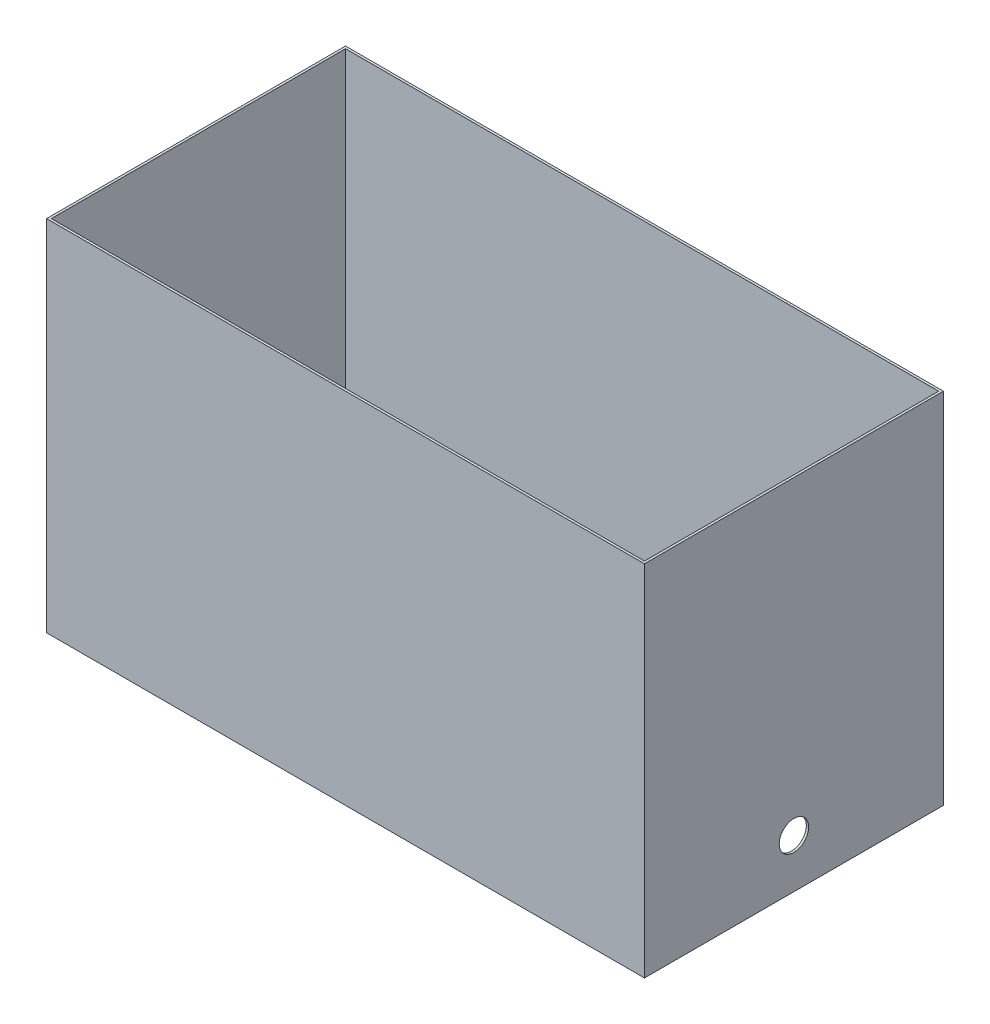
SolidWorks part; units mm, degrees
material "Galvanized Steel"
ref_plane "Front Plane" through (0, 0, 0) normal (0, 0, 1) x (1, 0, 0)
ref_plane "Top Plane" through (0, 0, 0) normal (0, 1, 0) x (1, 0, 0)
ref_plane "Right Plane" through (0, 0, 0) normal (1, 0, 0) x (0, 0, -1)
sketch "Sketch1" plane through (0, 0, 0) normal (0, 1, 0) x (1, 0, 0)
  line L0 (-252, 125) -> (252, 125)
  line L1 (-254, -127) -> (254, -127)
  line L2 (-254, -127) -> (-254, 127)
  line L3 (-254, 127) -> (254, 127)
  line L4 (254, -127) -> (254, 127)
  line L5 (-254, -127) -> (254, 127) construction
  line L6 (-254, 127) -> (254, -127) construction
  line L7 (252, -125) -> (252, 125)
  line L8 (-252, -125) -> (252, -125)
  line L9 (-252, -125) -> (-252, 125)
  point P0 (0, 0)
  dimension "D1" = 254
  dimension "D2" = 508
  dimension "D3" = 2
extrude "Boss-Extrude1" add sketch "Sketch1" along normal blind 304.8
sketch "Sketch2" plane through (-254, 0, 0) normal (-1, 0, 0) x (0, 0, 1)
  line L0 (0, 41.4) -> (0, 0) construction
  line L1 (-127, 0) -> (127, 0) construction
  circle A0 centre (0, 41.4) radius 12.5
  dimension "D1" = 41.4
  dimension "D2" = 25
extrude "Cut-Extrude1" cut sketch "Sketch2" against normal through all
